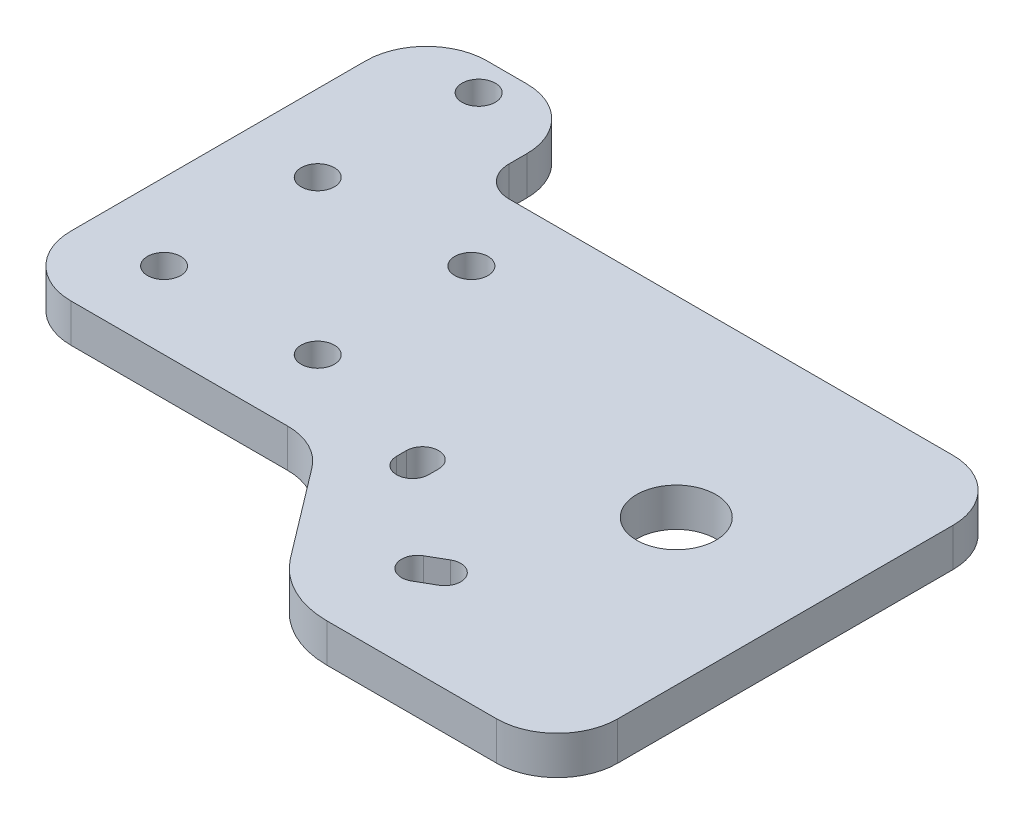
SolidWorks part; units mm, degrees
ref_plane "Front" through (0, 0, 0) normal (0, 0, 1) x (1, 0, 0)
ref_plane "Top" through (0, 0, 0) normal (0, 1, 0) x (1, 0, 0)
ref_plane "Right" through (0, 0, 0) normal (1, 0, 0) x (0, 0, -1)
sketch "Sketch1" plane through (0, 0, 0) normal (0, 1, 0) x (1, 0, 0)
  line L0 (0, 0) -> (89.6212, 0) construction
  line L1 (25.4, -25.4) -> (-25.4, -25.4)
  line L2 (25.4, -25.4) -> (25.4, 25.4) construction
  line L3 (25.4, 25.4) -> (-25.4, 25.4) construction
  line L4 (-25.4, -25.4) -> (-25.4, 25.4)
  line L5 (25.4, -25.4) -> (-25.4, 25.4) construction
  line L6 (25.4, 25.4) -> (-25.4, -25.4) construction
  line L7 (1.2, 25.4) -> (1.2, 76.2) construction
  line L8 (-12.7, 25.4) -> (-12.7, -25.4) construction
  line L9 (12.7, -25.4) -> (12.7, 25.4) construction
  line L10 (0, 0) -> (-25.4, 0) construction
  line L11 (-12.7, 0) -> (-12.7, 25.4) construction
  line L12 (-12.7, 12.7) -> (12.7, 12.7) construction
  line L13 (38.1, -41.4) -> (89.6212, -41.4) construction
  line L14 (86.6212, -27.36) -> (44.6212, -27.36) construction
  line L15 (86.6212, -27.36) -> (86.6212, 14.64) construction
  line L16 (86.6212, 14.64) -> (44.6212, 14.64) construction
  line L17 (44.6212, -27.36) -> (44.6212, 14.64) construction
  line L18 (86.6212, -27.36) -> (44.6212, 14.64) construction
  line L19 (86.6212, 14.64) -> (44.6212, -27.36) construction
  line L20 (81.1212, -21.86) -> (50.1212, -21.86) construction
  line L21 (81.1212, -21.86) -> (81.1212, 9.14) construction
  line L22 (81.1212, 9.14) -> (50.1212, 9.14) construction
  line L23 (50.1212, -21.86) -> (50.1212, 9.14) construction
  line L24 (81.1212, -21.86) -> (50.1212, 9.14) construction
  line L25 (81.1212, 9.14) -> (50.1212, -21.86) construction
  line L26 (89.6212, -41.4) -> (89.6212, 0) construction
  line L27 (36.4, -12.72) -> (65.6212, -12.72) construction
  line L28 (35.1664, -25.3192) -> (52.7755, -28.8008) construction
  line L29 (25.4, -25.4) -> (39.5919, -44.1062)
  line L30 (65.6212, 0) -> (0, 0) construction
  line L31 (1.2, 76.2) -> (-49.6, 76.2) construction
  line L32 (51.5419, -50.04) -> (89.6212, -50.04)
  line L33 (89.6212, -50.04) -> (89.6212, 25.4)
  line L34 (89.6212, 25.4) -> (25.4, 25.4)
  line L35 (36.4, -19.08) -> (36.4, -20.72) construction
  line L36 (51.5419, -35.04) -> (54.3783, -33.4) construction
  line L37 (51.5419, -35.04) -> (51.5419, -50.04) construction
  line L38 (-49.6, 76.2) -> (-49.6, 25.4) construction
  line L39 (-49.6, -25.4) -> (-25.4, -25.4) construction
  line L40 (-49.6, 25.4) -> (-25.4, 25.4) construction
  line L41 (-11.5, 25.4) -> (-11.5, 76.2) construction
  line L42 (-25.4, 25.4) -> (-25.4, 43.35)
  line L43 (-25.4, 43.35) -> (1.2, 43.35)
  line L44 (1.2, 43.35) -> (1.2, 25.4)
  line L45 (1.2, 25.4) -> (25.4, 25.4)
  circle A0 centre (-12.7, 12.7) radius 2.5 construction
  circle A1 centre (12.7, 12.7) radius 2.5 construction
  circle A2 centre (-12.7, -12.7) radius 2.5 construction
  circle A3 centre (12.7, -12.7) radius 2.5 construction
  circle A4 centre (65.6212, -6.36) radius 6.36 construction
  circle A5 centre (65.6212, -6.36) radius 11 construction
  circle A6 centre (50.1212, 9.14) radius 1.5 construction
  circle A7 centre (81.1212, 9.14) radius 1.5 construction
  circle A8 centre (81.1212, -21.86) radius 1.5 construction
  circle A9 centre (50.1212, -21.86) radius 1.5 construction
  circle A10 centre (51.5419, -35.04) radius 6.36 construction
  circle A11 centre (51.5419, -35.04) radius 11 construction
  circle A12 centre (36.4, -19.08) radius 6.36 construction
  circle A13 centre (36.4, -19.08) radius 11 construction
  circle A14 centre (50.1212, -21.86) radius 3 construction
  circle A15 centre (-11.5, 38.1) radius 2.5 construction
  circle A16 centre (-11.5, 38.1) radius 5.25 construction
  circle A19 centre (36.4, -19.08) radius 2.5 construction
  circle A20 centre (51.5419, -35.04) radius 2.5 construction
  circle A21 centre (65.6212, -6.36) radius 11 construction
  arc A22 (39.5919, -44.1062) -> (51.5419, -50.04) centre (51.5419, -35.04) ccw
  circle A23 centre (36.4, -20.72) radius 8 construction
  circle A24 centre (36.4, -20.72) radius 11 construction
  circle A25 centre (54.3783, -33.4) radius 8 construction
  circle A26 centre (54.3783, -33.4) radius 11 construction
  point P0 (0, 0)
  dimension "D6" = 5
  dimension "D7" = 12.72
  dimension "D9" = 22
  dimension "D11" = 3
  dimension "D12" = 16
  dimension "D13" = 6
  dimension "D16" = 12.7
  dimension "D17" = 5
  dimension "D18" = 22
  dimension "D20" = 16
  dimension "D21" = 4
  dimension "D23" = 10.5
  dimension "D1" = 50.8
  dimension "D2" = 50.8
  dimension "D3" = 50.8
  dimension "D4" = 12.7
  dimension "D5" = 25.4
  dimension "D8" = 42
  dimension "D10" = 31
  dimension "D14" = 50.8
  dimension "D15" = 24.2
  dimension "D19" = 3
  dimension "D22" = 12.7
extrude "Boss-Extrude1" add sketch "Sketch1" along normal blind 6.35
hole_wizard "M5 Clearance Hole1" positions "Sketch3" profile "Sketch2" hole size "M5" standard "ISO" end condition through all
sketch "Sketch3" plane through (0, 6.35, 0) normal (0, 1, 0) x (1, 0, 0)
  point P0 (-12.7, 12.7)
  point P3 (12.7, 12.7)
  point P6 (12.7, -12.7)
  point P9 (-12.7, -12.7)
  point P15 (-11.5, 38.1)
sketch "Sketch2" plane through (-12.7, 6.35, -12.7) normal (1, 0, 0) x (0, 0, 1)
  line L0 (0, 0) -> (0, 6.35)
  line L1 (0, 6.35) -> (2.75, 6.35)
  line L2 (2.75, 6.35) -> (2.75, 0)
  line L5 (2.75, 0) -> (0, 0)
  line L11 (0, -6.35) -> (0, 107.95) construction
  dimension "Thru Hole Dia." = 5.5
  dimension "Thru Hole Depth" = 6.35
sketch "Sketch7" plane through (0, 6.35, 0) normal (0, 1, 0) x (1, 0, 0)
  line L0 (36.4, -19.08) -> (36.4, -20.72) construction
  line L1 (54.3783, -33.4) -> (51.5419, -35.04) construction
  line L2 (53.0518, -31.1059) -> (50.2155, -32.7459)
  line L3 (33.75, -19.08) -> (33.75, -20.72)
  line L4 (55.7047, -35.6941) -> (52.8684, -37.3341)
  line L5 (39.05, -19.08) -> (39.05, -20.72)
  arc A0 (53.0518, -31.1059) -> (55.7047, -35.6941) centre (54.3783, -33.4) cw
  arc A1 (50.2155, -32.7459) -> (52.8684, -37.3341) centre (51.5419, -35.04) ccw
  arc A2 (33.75, -19.08) -> (39.05, -19.08) centre (36.4, -19.08) cw
  arc A3 (33.75, -20.72) -> (39.05, -20.72) centre (36.4, -20.72) ccw
  dimension "D1" = 2.65
  dimension "D2" = 2.65
extrude "Cut-Extrude2" cut sketch "Sketch7" against normal through all
fillet "Fillet1" radius 10 6 edges at (89.6212, 3.175, 50.04) (89.6212, 3.175, -25.4) (25.4, 3.175, 25.4) (-25.4, 3.175, 25.4) (-25.4, 3.175, -43.35) (1.2, 3.175, -43.35)
sketch "Sketch10" plane through (0, 6.35, 0) normal (0, 1, 0) x (1, 0, 0)
  circle A0 centre (65.6212, -6.36) radius 6.55
  dimension "D1" = 13.1
extrude "Cut-Extrude3" cut sketch "Sketch10" against normal through all
fillet "Fillet2" radius 5 1 edges at (1.2, 3.175, -25.4)
